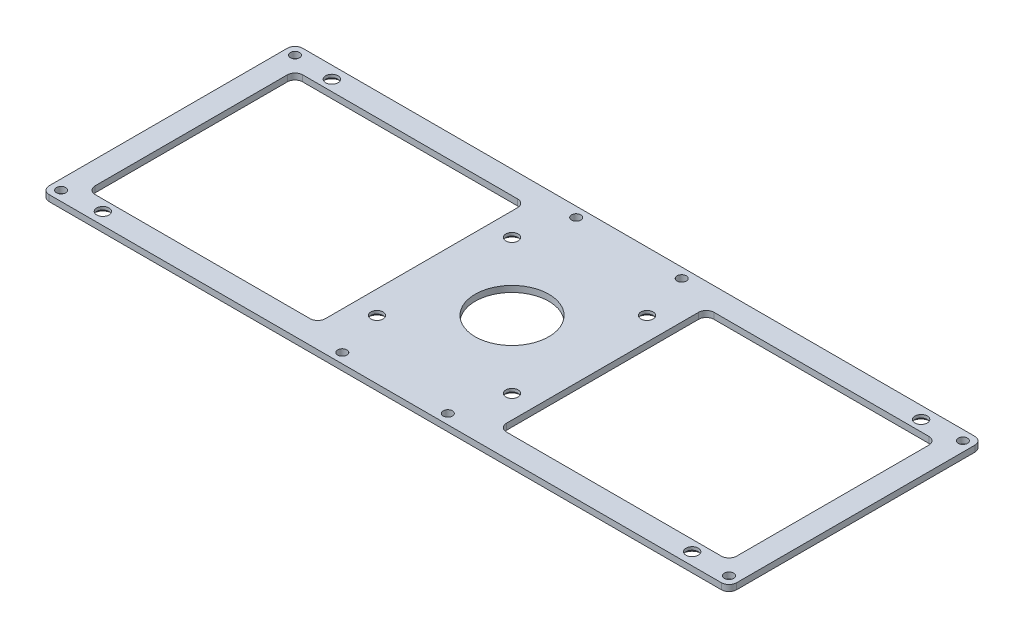
SolidWorks part; units mm, degrees
note: The reader was unsure of these and kept them because the rebuilt part matched: thickness of "Base-Flange1", "Sheet-Metal1", "Sheet-Metal2", "Sheet-Metal6", "Sheet-Metal7", "Sheet-Metal8", "Sheet-Metal9", "Sheet-Metal10", "Sheet-Metal11".
material "6061-T6 (SS)"
ref_plane "Front Plane" through (0, 0, 0) normal (0, 0, 1) x (1, 0, 0)
ref_plane "Top Plane" through (0, 0, 0) normal (0, 1, 0) x (1, 0, 0)
ref_plane "Right Plane" through (0, 0, 0) normal (1, 0, 0) x (0, 0, -1)
sketch "Sketch1" plane through (0, 0, 0) normal (0, 1, 0) x (1, 0, 0)
  line L1 (-60.9596, 49.4555) -> (139.0404, 49.4555)
  line L2 (-60.9596, 49.4555) -> (-60.9596, -33.1445)
  line L3 (-60.9596, -33.1445) -> (139.0404, -33.1445)
  line L4 (139.0404, 49.4555) -> (139.0404, -33.1445)
  dimension "D1" = 82.6
  dimension "D2" = 200
base flange "Base-Flange1" sketch "Sketch1" thickness 2 reverse thickness direction no parameters "D1"=1
sketch "Sketch6" plane through (0, 0, 0) normal (0, 1, 0) x (1, 0, 0)
  line L0 (139.0404, 49.4555) -> (-60.9596, 49.4555) construction
  line L1 (-60.9596, 49.4555) -> (-60.9596, -33.1445) construction
  line L2 (139.0404, -33.1445) -> (139.0404, 49.4555) construction
  line L3 (-60.9596, -33.1445) -> (139.0404, -33.1445) construction
  circle A0 centre (-56.9596, 45.4555) radius 2
  circle A1 centre (-56.9596, -29.1445) radius 2
  circle A2 centre (135.0404, -29.1445) radius 2
  circle A3 centre (135.0404, 45.4555) radius 2
  dimension "D1" = 4
  dimension "D2" = 4
  dimension "D3" = 4
  dimension "D4" = 4
  dimension "D5" = 4
extrude "Cut-Extrude1" cut sketch "Sketch6" against normal through all normal cut yes
sketch "Sketch7" plane through (0, 0, 0) normal (0, 1, 0) x (1, 0, 0)
  line L0 (-60.9596, 49.4555) -> (-60.9596, -33.1445) construction
  line L1 (139.0404, 49.4555) -> (-60.9596, 49.4555) construction
  circle A0 centre (39.0404, 8.1555) radius 12
  point P5 (-60.9596, 8.1555)
  point P9 (39.0404, 49.4555)
  dimension "D1" = 24
extrude "Cut-Extrude2" cut sketch "Sketch7" against normal through all normal cut yes
sketch "Sketch8" plane through (0, 0, 0) normal (0, 1, 0) x (1, 0, 0)
  line L0 (17.0404, -13.8445) -> (9.5404, -13.8445) construction
  line L1 (17.0404, -13.8445) -> (61.0404, -13.8445) construction
  line L2 (17.0404, -13.8445) -> (17.0404, 30.1555) construction
  line L3 (17.0404, 30.1555) -> (61.0404, 30.1555) construction
  line L4 (61.0404, -13.8445) -> (61.0404, 30.1555) construction
  line L5 (17.0404, -13.8445) -> (61.0404, 30.1555) construction
  line L6 (17.0404, 30.1555) -> (61.0404, -13.8445) construction
  line L7 (-53.4596, 41.9555) -> (9.5404, 41.9555)
  line L8 (-53.4596, 41.9555) -> (-53.4596, -25.6445)
  line L9 (-53.4596, -25.6445) -> (9.5404, -25.6445)
  line L10 (9.5404, 41.9555) -> (9.5404, -25.6445)
  line L11 (68.5404, -25.6445) -> (131.5404, -25.6445)
  line L12 (68.5404, -25.6445) -> (68.5404, 41.9555)
  line L13 (68.5404, 41.9555) -> (131.5404, 41.9555)
  line L14 (131.5404, -25.6445) -> (131.5404, 41.9555)
  line L15 (61.0404, -13.8445) -> (68.5404, -13.8445) construction
  line L16 (139.0404, 49.4555) -> (-60.9596, 49.4555) construction
  line L17 (-60.9596, -33.1445) -> (139.0404, -33.1445) construction
  line L18 (-60.9596, 49.4555) -> (-60.9596, -33.1445) construction
  line L19 (139.0404, -33.1445) -> (139.0404, 49.4555) construction
  circle A0 centre (17.0404, 30.1555) radius 2
  circle A1 centre (61.0404, 30.1555) radius 2
  circle A2 centre (61.0404, -13.8445) radius 2
  circle A3 centre (17.0404, -13.8445) radius 2
  point P0 (39.0404, 8.1555)
  dimension "D3" = 4
  dimension "D1" = 44
  dimension "D2" = 44
  dimension "D4" = 7.5
  dimension "D5" = 7.5
  dimension "D6" = 7.5
  dimension "D7" = 7.5
  dimension "D8" = 7.5
extrude "Cut-Extrude3" cut sketch "Sketch8" against normal through all normal cut yes
chamfer "Chamfer1" distance 1 angle 45 8 edges at (135.0404, -2, 31.1445) (135.0404, -2, -43.4555) (-56.9596, -2, -43.4555) (-56.9596, -2, 31.1445) (17.0404, -2, -28.1555) (61.0404, -2, -28.1555) (61.0404, -2, 15.8445) (17.0404, -2, 15.8445)
sketch "Sketch10" plane through (-60.9596, 0, 0) normal (-1, 0, 0) x (0, 0, 1)
  line L1 (33.1445, 0) -> (-49.4555, 0)
  line L2 (33.1445, 0) -> (33.1445, -2)
  line L3 (33.1445, -2) -> (-49.4555, -2)
  line L4 (-49.4555, 0) -> (-49.4555, -2)
extrude "Boss-Extrude1" add sketch "Sketch10" along normal blind 12
sketch "Sketch11" plane through (139.0404, 0, 0) normal (1, 0, 0) x (0, 0, -1)
  line L1 (-33.1445, -2) -> (49.4555, -2)
  line L2 (-33.1445, -2) -> (-33.1445, 0)
  line L3 (-33.1445, 0) -> (49.4555, 0)
  line L4 (49.4555, -2) -> (49.4555, 0)
extrude "Boss-Extrude2" add sketch "Sketch11" along normal blind 12
sketch "Sketch12" plane through (0, 0, 0) normal (0, 1, 0) x (1, 0, 0)
  line L0 (-53.4596, 41.9555) -> (-65.4596, 41.9555)
  line L1 (-65.4596, 41.9555) -> (-65.4596, -25.6445)
  line L2 (-65.4596, -25.6445) -> (-53.4596, -25.6445)
  line L3 (-53.4596, -25.6445) -> (-53.4596, 41.9555)
  line L4 (131.5404, 41.9555) -> (143.5404, 41.9555)
  line L5 (143.5404, 41.9555) -> (143.5404, -25.6445)
  line L6 (143.5404, -25.6445) -> (131.5404, -25.6445)
  line L7 (131.5404, -25.6445) -> (131.5404, 41.9555)
  line L8 (151.0404, 49.4555) -> (151.0404, -33.1445) construction
  line L9 (-72.9596, -33.1445) -> (-72.9596, 49.4555) construction
  dimension "D1" = 7.5
  dimension "D2" = 7.5
extrude "Cut-Extrude4" cut sketch "Sketch12" against normal through all normal cut yes
fillet "Fillet2" radius 2.5 12 edges at (68.5404, -1, -41.9555) (151.0404, -1, -49.4555) (143.5404, -1, -41.9555) (151.0404, -1, 33.1445) (143.5404, -1, 25.6445) (68.5404, -1, 25.6445) (9.5404, -1, 25.6445) (-72.9596, -1, 33.1445) (-65.4596, -1, 25.6445) (9.5404, -1, -41.9555) (-65.4596, -1, -41.9555) (-72.9596, -1, -49.4555)
hole_wizard "Ø3.0mm Dowel Hole1" positions "Sketch13" profile "Sketch14" hole size "Ø3.0" standard "ANSI Metric" end condition through all
sketch "Sketch13" plane through (0, -2, 0) normal (0, -1, 0) x (-1, 0, 0)
  point P0 (69.7596, -29.9445)
  point P3 (69.7596, 46.2555)
  point P6 (-21.8404, 46.2555)
  point P9 (-21.8404, -29.9445)
  point P12 (-56.2404, 46.2555)
  point P15 (-56.2404, -29.9445)
  point P18 (-147.8404, -29.9445)
  point P21 (-147.8404, 46.2555)
sketch "Sketch14" plane through (-69.7596, -2, 29.9445) normal (1, 0, 0) x (0, 0, -1)
  line L0 (0, 0) -> (0, 2)
  line L1 (0, 2) -> (1.5, 2)
  line L2 (1.5, 2) -> (1.5, 0)
  line L5 (1.5, 0) -> (0, 0)
  line L11 (0, -6.35) -> (0, 107.95) construction
  dimension "Thru Hole Dia." = 3
  dimension "Thru Hole Depth" = 2
sketch "Bend-Lines1" [suppressed] plane through (0, 0, 0) normal (0, 1, 0) x (1, 0, 0)
sketch "Bounding-Box1" [suppressed] plane through (0, 0, 0) normal (0, 1, 0) x (1, 0, 0)
sheet metal parameters "Sheet-Metal1" thickness 2 parameters "D1"=1
flat pattern "Flat-Pattern1" [suppressed]
sketch "Bend-Lines2" plane through (0, 0, 0) normal (0, 1, 0) x (1, 0, 0)
sketch3d "Bounding-Box2" [suppressed]
  line L0 (-162.0404, -38.5445, 0) -> (60.9596, -38.5445, 0) construction
  line L1 (-162.0404, 49.4555, 0) -> (60.9596, 49.4555, 0) construction
  line L2 (-162.0404, -38.5445, 0) -> (-162.0404, 49.4555, 0) construction
  line L3 (60.9596, -38.5445, 0) -> (60.9596, 49.4555, 0) construction
sheet metal parameters "Sheet-Metal2" thickness 2 parameters "D1"=1
flat pattern "Flat-Pattern1"
sketch "Bend-Lines2" plane through (0, 0, 0) normal (0, 1, 0) x (1, 0, 0)
sketch3d "Bounding-Box2" [suppressed]
  line L0 (-60.9596, -31.5444, 0) -> (162.0404, -31.5445, 0) construction
  line L1 (-60.9595, 49.4555, 0) -> (162.0405, 49.4554, 0) construction
  line L2 (-60.9596, -31.5444, 0) -> (-60.9595, 49.4555, 0) construction
  line L3 (162.0404, -31.5445, 0) -> (162.0405, 49.4554, 0) construction
sheet metal parameters "Sheet-Metal6" thickness 2 parameters "D1"=1
flat pattern "Flat-Pattern1"
sketch "Bend-Lines2" plane through (0, 0, 0) normal (0, 1, 0) x (1, 0, 0)
sketch3d "Bounding-Box2" [suppressed]
  line L0 (-60.9596, -31.5444, 0) -> (162.0404, -31.5445, 0) construction
  line L1 (-60.9595, 49.4555, 0) -> (162.0405, 49.4554, 0) construction
  line L2 (-60.9596, -31.5444, 0) -> (-60.9595, 49.4555, 0) construction
  line L3 (162.0404, -31.5445, 0) -> (162.0405, 49.4554, 0) construction
sheet metal parameters "Sheet-Metal7" thickness 2 parameters "D1"=1
flat pattern "Flat-Pattern1"
sketch "Bend-Lines2" plane through (0, 0, 0) normal (0, 1, 0) x (1, 0, 0)
sketch3d "Bounding-Box2" [suppressed]
  line L0 (139.0404, -33.1445, 0) -> (-60.9596, -33.1445, 0) construction
  line L1 (139.0404, 49.4555, 0) -> (-60.9596, 49.4555, 0) construction
  line L2 (139.0404, -33.1445, 0) -> (139.0404, 49.4555, 0) construction
  line L3 (-60.9596, -33.1445, 0) -> (-60.9596, 49.4555, 0) construction
sheet metal parameters "Sheet-Metal8" thickness 2 parameters "D1"=1
flat pattern "Flat-Pattern1"
sketch "Bend-Lines2" plane through (0, 0, 0) normal (0, 1, 0) x (1, 0, 0)
sketch3d "Bounding-Box2" [suppressed]
  line L0 (139.0404, -33.1445, 0) -> (-72.9596, -33.1445, 0) construction
  line L1 (139.0404, 49.4555, 0) -> (-72.9596, 49.4555, 0) construction
  line L2 (139.0404, -33.1445, 0) -> (139.0404, 49.4555, 0) construction
  line L3 (-72.9596, -33.1445, 0) -> (-72.9596, 49.4555, 0) construction
sheet metal parameters "Sheet-Metal9" thickness 2 parameters "D1"=1
flat pattern "Flat-Pattern1"
sketch "Bend-Lines2" plane through (0, 0, 0) normal (0, 1, 0) x (1, 0, 0)
sketch3d "Bounding-Box2" [suppressed]
  line L0 (151.0404, -33.1445, 0) -> (-72.9596, -33.1445, 0) construction
  line L1 (151.0404, 49.4555, 0) -> (-72.9596, 49.4555, 0) construction
  line L2 (151.0404, -33.1445, 0) -> (151.0404, 49.4555, 0) construction
  line L3 (-72.9596, -33.1445, 0) -> (-72.9596, 49.4555, 0) construction
sheet metal parameters "Sheet-Metal10" thickness 2 parameters "D1"=1
flat pattern "Flat-Pattern1"
sketch "Bend-Lines2" plane through (0, 0, 0) normal (0, 1, 0) x (1, 0, 0)
sketch3d "Bounding-Box2" [suppressed]
  line L0 (-72.9596, -33.1445, 0) -> (151.0404, -33.1445, 0) construction
  line L1 (-72.9596, 49.4555, 0) -> (151.0404, 49.4555, 0) construction
  line L2 (-72.9596, -33.1445, 0) -> (-72.9596, 49.4555, 0) construction
  line L3 (151.0404, -33.1445, 0) -> (151.0404, 49.4555, 0) construction
sheet metal parameters "Sheet-Metal11" thickness 2 parameters "D1"=1
flat pattern "Flat-Pattern1"
sketch "Bend-Lines2" plane through (0, 0, 0) normal (0, 1, 0) x (1, 0, 0)
sketch3d "Bounding-Box2" [suppressed]
  line L0 (-72.9596, -33.1445, 0) -> (151.0404, -33.1445, 0) construction
  line L1 (-72.9596, 49.4555, 0) -> (151.0404, 49.4555, 0) construction
  line L2 (-72.9596, -33.1445, 0) -> (-72.9596, 49.4555, 0) construction
  line L3 (151.0404, -33.1445, 0) -> (151.0404, 49.4555, 0) construction
